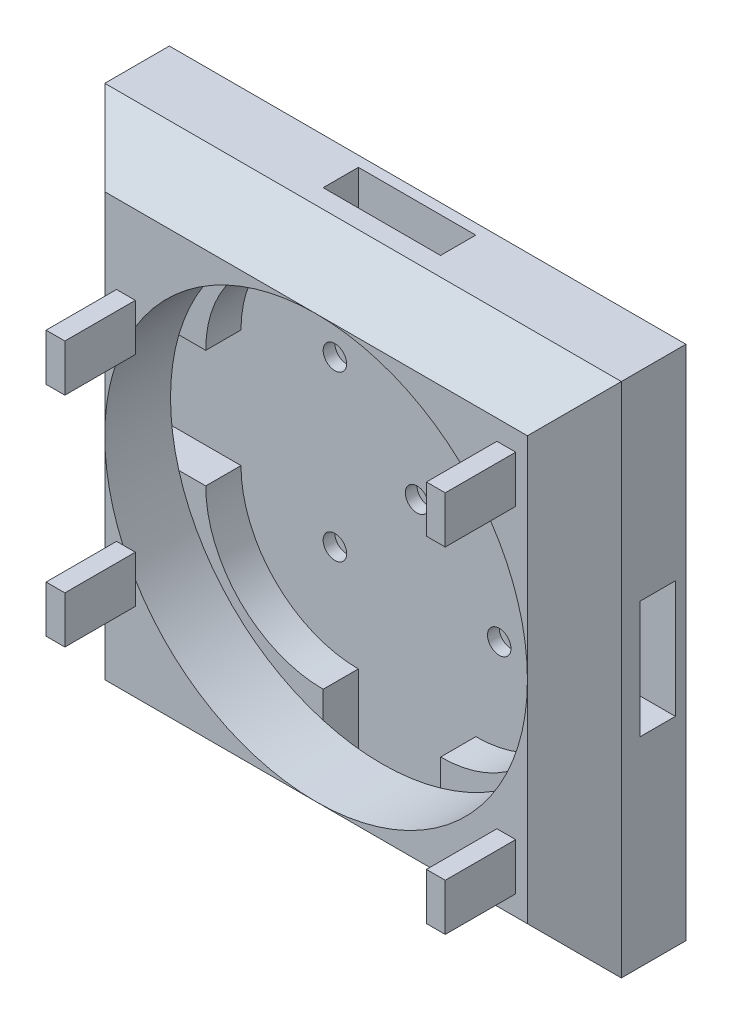
SolidWorks part; units mm, degrees
material "3.0205 (EN-AW 1200)"
ref_plane "정면" through (0, 0, 0) normal (0, 0, 1) x (1, 0, 0)
ref_plane "윗면" through (0, 0, 0) normal (0, 1, 0) x (1, 0, 0)
ref_plane "우측면" through (0, 0, 0) normal (1, 0, 0) x (0, 0, -1)
sketch "스케치1" plane through (0, 0, 0) normal (0, 0, 1) x (1, 0, 0)
  line L1 (-110, 110) -> (110, 110)
  line L2 (-110, 110) -> (-110, -110)
  line L3 (-110, -110) -> (110, -110)
  line L4 (110, 110) -> (110, -110)
  line L5 (-110, 110) -> (110, -110) construction
  line L6 (-110, -110) -> (110, 110) construction
  point P0 (0, 0)
  dimension "D1" = 220
  dimension "D2" = 220
extrude "보스-돌출1" add sketch "스케치1" along normal blind 20 draft 45
sketch "스케치2" plane through (0, 0, 20) normal (0, 0, 1) x (1, 0, 0)
  line L1 (-85, 56.45) -> (-77, 56.45)
  line L2 (-85, 56.45) -> (-85, 36.45)
  line L3 (-85, 36.45) -> (-77, 36.45)
  line L4 (-77, 56.45) -> (-77, 36.45)
  line L6 (-90, 90) -> (-90, -90) construction
  line L11 (11, 0) -> (-11, 0) construction
  line L16 (-77, -56.45) -> (-77, -36.45)
  line L17 (-85, -36.45) -> (-77, -36.45)
  line L18 (-85, -56.45) -> (-85, -36.45)
  line L19 (-85, -56.45) -> (-77, -56.45)
  line L20 (-110, -110) -> (110, -110) construction
  line L21 (77, 81.45) -> (85, 81.45)
  line L22 (77, 81.45) -> (77, 61.45)
  line L23 (77, 61.45) -> (85, 61.45)
  line L24 (85, 81.45) -> (85, 61.45)
  line L25 (77, -61.45) -> (85, -61.45)
  line L26 (77, -61.45) -> (77, -81.45)
  line L27 (77, -81.45) -> (85, -81.45)
  line L28 (85, -61.45) -> (85, -81.45)
  line L29 (110, 110) -> (-110, 110) construction
  line L32 (90, -90) -> (90, 90) construction
  dimension "D1" = 8
  dimension "D2" = 20
  dimension "D3" = 5
  dimension "D4" = 13
  dimension "D5" = 28.55
  dimension "D6" = 20
  dimension "D7" = 20
  dimension "D8" = 28.55
  dimension "D9" = 8
  dimension "D10" = 8
  dimension "D11" = 13
  dimension "D12" = 13
extrude "보스-돌출2" add sketch "스케치2" along normal blind 30 and the other way up to surface (20 mm away) other way up to face at (0, 0, 0)
sketch "스케치3" plane through (0, 0, 20) normal (0, 0, 1) x (1, 0, 0)
  text T0 "WAYUP\r\n" font "Century Gothic" height 20
sketch "스케치4" plane through (0, 0, 0) normal (0, 0, -1) x (-1, 0, 0)
  line L1 (-110, 110) -> (110, 110)
  line L2 (-110, 110) -> (-110, -110)
  line L3 (-110, -110) -> (110, -110)
  line L4 (110, 110) -> (110, -110)
extrude "보스-돌출3" add sketch "스케치4" along normal blind 30
ref_plane "평면1" through (0, 0, -23) normal (0, 0, -1) x (-1, 0, 0)
sketch "스케치6" plane through (0, 0, -23) normal (0, 0, -1) x (-1, 0, 0)
  line L0 (-110, 25) -> (-75, 25)
  line L1 (-110, 110) -> (-110, -110) construction
  line L2 (25, 110) -> (25, 75)
  line L3 (110, -25) -> (75, -25)
  line L4 (-25, -110) -> (-25, -75)
  line L5 (-75, -25) -> (-110, -25)
  line L6 (-110, -25) -> (-110, 25)
  line L7 (25, -75) -> (25, -110)
  line L8 (-110, -110) -> (110, -110) construction
  line L9 (25, -110) -> (-25, -110)
  line L10 (110, -25) -> (110, 25)
  line L11 (110, -110) -> (110, 110) construction
  line L12 (110, 25) -> (75, 25)
  line L13 (25, 110) -> (-25, 110)
  line L14 (110, 110) -> (-110, 110) construction
  line L15 (-25, 110) -> (-25, 75)
  arc A0 (-75, 25) -> (-25, 75) centre (-25, 25) cw
  arc A1 (25, 75) -> (75, 25) centre (25, 25) cw
  arc A2 (75, -25) -> (25, -75) centre (25, -25) cw
  arc A3 (-25, -75) -> (-75, -25) centre (-25, -25) cw
  point P21 (0, 0)
  dimension "D3" = 50
  dimension "D2" = 50
  dimension "D4" = 0
  dimension "D1" = 4
extrude "컷-돌출1" cut sketch "스케치6" against normal blind 15
sketch "스케치7" plane through (0, 0, 20) normal (0, 0, 1) x (1, 0, 0)
  circle A0 centre (0, 0) radius 90
  dimension "D1" = 180
extrude "컷-돌출2" cut sketch "스케치7" against normal blind 28
sketch "스케치9" plane through (0, 0, -23) normal (0, 0, 1) x (1, 0, 0)
  line L4 (11, 0) -> (-11, 0) construction
  circle A0 centre (-35, 35) radius 5
  circle A1 centre (0, 0) radius 5
  circle A2 centre (35, 35) radius 5
  circle A5 centre (-35, -35) radius 5 [skipped]
  circle A6 centre (35, -35) radius 5 [skipped]
  circle A7 centre (35, -35) radius 5
  circle A8 centre (-35, -35) radius 5
  point P15 (0, 0)
  dimension "D1" = 10
  dimension "D7" = 10
  dimension "D2" = 40
  dimension "D3" = 40
  dimension "D5" = 40
  dimension "D6" = 40
  dimension "D4" = 4
extrude "컷-돌출3" cut sketch "스케치9" against normal blind 5
sketch "스케치10" plane through (0, 110, 0) normal (0, 1, 0) x (1, 0, 0)
  line L0 (-110, 30) -> (-110, 27.5)
  line L1 (-110, 30) -> (-110, 0) construction
  line L2 (-110, 27.5) -> (-107.5, 30)
  line L3 (-110, 30) -> (110, 30) construction
  line L4 (-107.5, 30) -> (-110, 30)
  dimension "D1" = 2.5
  dimension "D2" = 2.5
extrude "컷-돌출4" cut sketch "스케치10" against normal through all
sketch "스케치11" plane through (0, 0, 0) normal (0, 1, 0) x (1, 0, 0)
  line L0 (0, -68.4326) -> (0, 99.1854) construction
pattern_circular "원형 패턴2" count 4 over 360 about axis through (0, 0, 68.4326) along (0, 0, -1) of "컷-돌출4" reverse direction yes
